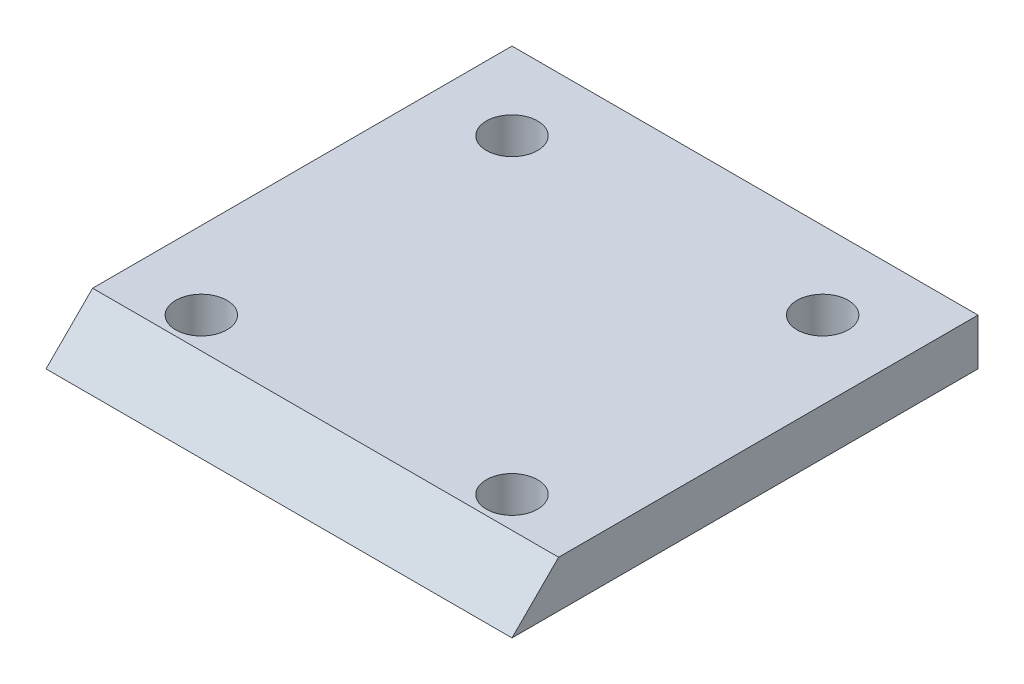
SolidWorks part; units mm, degrees
ref_plane "Front Plane" through (0, 0, 0) normal (0, 0, 1) x (1, 0, 0)
ref_plane "Top Plane" through (0, 0, 0) normal (0, 1, 0) x (1, 0, 0)
ref_plane "Right Plane" through (0, 0, 0) normal (1, 0, 0) x (0, 0, -1)
sketch "Sketch1" plane through (0, 0, 0) normal (0, 1, 0) x (1, 0, 0)
  line L1 (-15, -15) -> (15, -15)
  line L2 (-15, -15) -> (-15, 15)
  line L3 (-15, 15) -> (15, 15)
  line L4 (15, -15) -> (15, 15)
  line L5 (-15, -15) -> (15, 15) construction
  line L6 (-15, 15) -> (15, -15) construction
  point P0 (0, 0)
  dimension "D1" = 30
  dimension "D2" = 30
extrude "Boss-Extrude1" add sketch "Sketch1" along normal blind 3
hole_wizard "M4x0.7 Tapped Hole1" positions "Sketch3" profile "Sketch4" tap size "M4x0.7" standard "ANSI Metric" end condition through all
sketch "Sketch3" plane through (0, 3, 0) normal (0, 1, 0) x (1, 0, 0)
  line L1 (-10, -10) -> (10, -10)
  line L2 (-10, -10) -> (-10, 10)
  line L3 (-10, 10) -> (10, 10)
  line L4 (10, -10) -> (10, 10)
  line L5 (-10, -10) -> (10, 10) construction
  line L6 (-10, 10) -> (10, -10) construction
  point P57 (0, 0)
  point P60 (-10, 10)
  point P63 (10, 10)
  point P66 (10, -10)
  point P69 (-10, -10)
  dimension "D1" = 20
  dimension "D2" = 20
sketch "Sketch4" plane through (-10, 3, 10) normal (1, 0, 0) x (0, 0, 1)
  line L0 (0, 0) -> (0, 3)
  line L1 (0, 3) -> (1.65, 3)
  line L2 (1.65, 3) -> (1.65, 0)
  line L5 (1.65, 0) -> (0, 0)
  line L11 (0, -6.35) -> (0, 107.95) construction
  dimension "Thru Tap Drill Dia." = 3.3
  dimension "Thru Tap Drill Depth" = 3
chamfer "Chamfer2" distance 3 angle 45 1 edges at (0, 3, 15)
